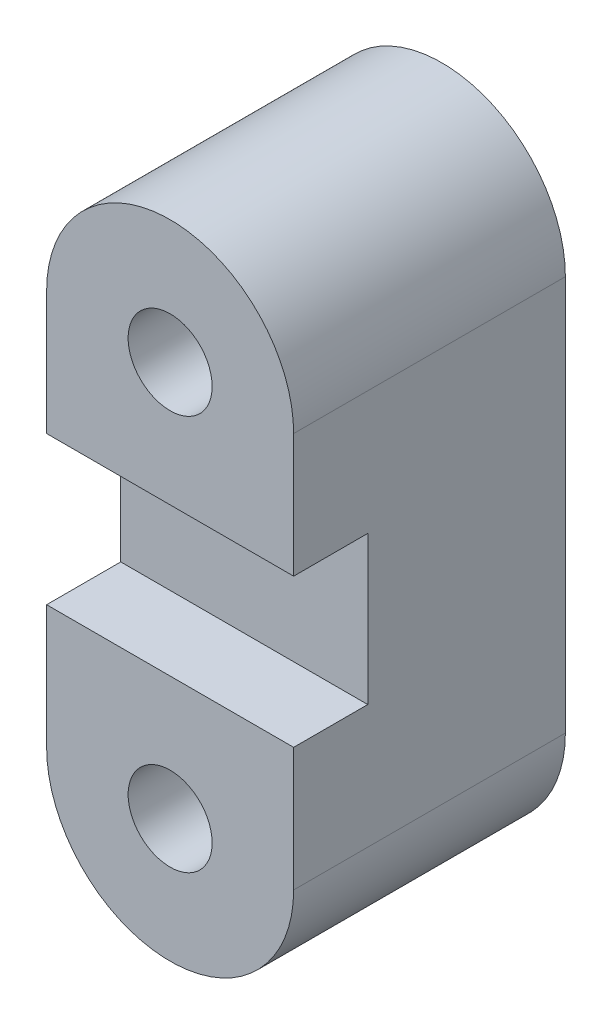
SolidWorks part; units mm, degrees
ref_plane "Front Plane" through (0, 0, 0) normal (0, 0, 1) x (1, 0, 0)
ref_plane "Top Plane" through (0, 0, 0) normal (0, 1, 0) x (1, 0, 0)
ref_plane "Right Plane" through (0, 0, 0) normal (1, 0, 0) x (0, 0, -1)
sketch "Sketch1" plane through (0, 0, 0) normal (0, 0, 1) x (1, 0, 0)
  line L0 (0, -8) -> (0, 8) construction
  line L1 (0, -8) -> (0, 8) construction
  line L2 (-5, -8) -> (-5, 8)
  line L3 (5, -8) -> (5, 8)
  circle A0 centre (0, 8) radius 1.7
  circle A1 centre (0, -8) radius 1.7
  arc A2 (-5, -8) -> (5, -8) centre (0, -8) ccw
  arc A3 (5, 8) -> (-5, 8) centre (0, 8) ccw
  point P4 (0, 0)
  dimension "D1" = 3.4
  dimension "D2" = 5
  dimension "D3" = 16
extrude "Boss-Extrude1" add sketch "Sketch1" along normal blind 11
sketch "Sketch2" plane through (0, 0, 11) normal (0, 0, 1) x (1, 0, 0)
  line L0 (-5, 8) -> (-5, -8) construction
  line L1 (5, -8) -> (5, 8) construction
  line L2 (-5, -3) -> (5, -3)
  line L3 (-5, -3) -> (-5, 3)
  line L4 (-5, 3) -> (5, 3)
  line L5 (5, -3) -> (5, 3)
  line L6 (0, 0) -> (-5, 0) construction
  dimension "D1" = 6
extrude "Cut-Extrude1" cut sketch "Sketch2" against normal blind 3
